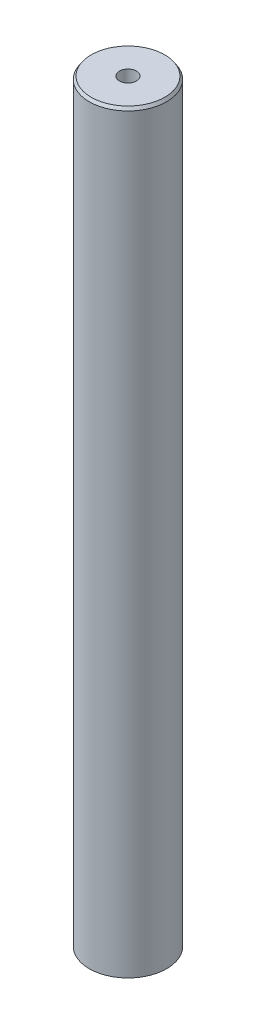
SolidWorks part; units mm, degrees
ref_plane "Front Plane" through (0, 0, 0) normal (0, 0, 1) x (1, 0, 0)
ref_plane "Top Plane" through (0, 0, 0) normal (0, 1, 0) x (1, 0, 0)
ref_plane "Right Plane" through (0, 0, 0) normal (1, 0, 0) x (0, 0, -1)
sketch "Sketch1" plane through (0, 0, 0) normal (0, 1, 0) x (1, 0, 0)
  circle A0 centre (0, 0) radius 5
  dimension "SHAFT_OD" = 10
extrude "Boss-Extrude1" add sketch "Sketch1" along normal blind 97.632
sketch "Sketch2" plane through (0, 0, 0) normal (0, 1, 0) x (1, 0, 0)
  circle A0 centre (0, 0) radius 1.1076
  dimension "BORE_D" = 2.2152
extrude "Cut-Extrude1" cut sketch "Sketch2" along normal through all
chamfer "Chamfer1" distance 0.3786 angle 33.273 2 edges at (0, 97.632, 5) (0, 0, 5) first distance on face at (0, 97.632, 5) first distance on face at (0, 0, 1.1076)
